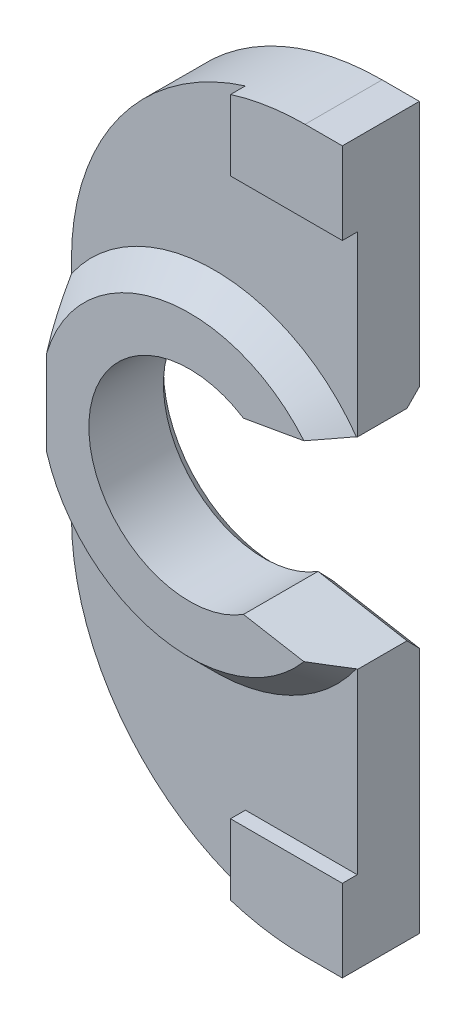
SolidWorks part; units mm, degrees
material "ABS"
ref_plane "Front Plane" through (0, 0, 0) normal (0, 0, 1) x (1, 0, 0)
ref_plane "Top Plane" through (0, 0, 0) normal (0, 1, 0) x (1, 0, 0)
ref_plane "Right Plane" through (0, 0, 0) normal (1, 0, 0) x (0, 0, -1)
sketch "Sketch2" plane through (0, 0, 0) normal (0, 0, 1) x (1, 0, 0)
  line L1 (5.75, -14.5) -> (4.25, -14.5)
  line L2 (5.75, -14.5) -> (5.75, -4.05)
  line L3 (5.75, 14.5) -> (4.25, 14.5)
  line L4 (-5.75, -4.5) -> (-5.75, 4.5)
  line L5 (5.75, -14.5) -> (1.4929, -3.7648) construction
  line L6 (5.75, 14.5) -> (1.606, 4.05) construction
  line L8 (5.75, 4.05) -> (5.75, 14.5)
  line L9 (0, 0) -> (-5.75, -14.5) construction
  line L10 (-1.4929, 3.7648) -> (-5.75, 14.5) construction
  line L11 (5.75, 4.05) -> (2.171, 3.4189)
  line L12 (5.75, -4.05) -> (2.171, -3.4189)
  arc A1 (4.25, -14.5) -> (-5.75, -4.5) centre (4.25, -4.5) cw
  arc A2 (-5.75, 4.5) -> (4.25, 14.5) centre (4.25, 4.5) cw
  arc A3 (2.171, 3.4189) -> (2.171, -3.4189) centre (0, 0) ccw
  point P0 (0, 0)
  dimension "D4" = 10
  dimension "D1" = 11.5
  dimension "D2" = 29
extrude "Boss-Extrude1" add sketch "Sketch2" along normal blind 2.5
sketch "Sketch3" plane through (0, 0, 2.5) normal (0, 0, 1) x (1, 0, 0)
  line L4 (-5.75, 4.5) -> (-5.75, -4.5) construction
  line L5 (-5.75, 1.7139) -> (-5.75, -1.7139)
  line L6 (2.171, 3.4189) -> (5.75, 4.05) construction
  line L7 (5.75, -4.05) -> (2.171, -3.4189) construction
  line L8 (2.171, 3.4189) -> (4.6037, 3.8479)
  line L9 (4.6037, -3.8479) -> (2.171, -3.4189)
  arc A1 (0, 4.05) -> (0, -4.05) centre (0, 0) ccw
  arc A2 (4.6037, 3.8479) -> (-5.75, 1.7139) centre (0, 0) ccw
  arc A3 (-5.75, -1.7139) -> (4.6037, -3.8479) centre (0, 0) ccw
  arc A4 (2.171, 3.4189) -> (2.171, -3.4189) centre (0, 0) ccw construction
  arc A5 (2.171, 3.4189) -> (2.171, -3.4189) centre (0, 0) ccw
  line M8 (-5.75, 4.5) -> (-5.75, -4.5)
  line M17 (5.75, -4.05) -> (2.171, -3.4189)
  arc M18 (2.171, -3.4189) -> (2.171, 3.4189) centre (0, 0) cw
  line M19 (2.171, 3.4189) -> (5.75, 4.05)
  dimension "D1" = 12
extrude "Boss-Extrude2" add sketch "Sketch3" along normal blind 1 contours A3 A2 M8 M17 M18 M19
sketch "Sketch4" plane through (0, 0, 2.5) normal (0, 0, 1) x (1, 0, 0)
  line L0 (5.75, 11.2) -> (1.25, 11.2)
  line L1 (1.25, 11.2) -> (1.25, 14.0394)
  line L5 (5.75, 4.05) -> (5.75, 14.5)
  line L6 (5.75, 14.5) -> (4.25, 14.5)
  line L7 (-5.75, 4.5) -> (-5.75, 1.7139)
  line L9 (5.75, 4.05) -> (5.75, 14.5)
  line L10 (5.75, 14.5) -> (4.25, 14.5)
  line L11 (-5.75, 4.5) -> (-5.75, 1.7139)
  line L15 (4.6037, 3.8479) -> (5.75, 4.05)
  line L16 (4.6037, 3.8479) -> (5.75, 4.05)
  arc A2 (4.6037, 3.8479) -> (-5.75, 1.7139) centre (0, 0) ccw
  arc A3 (4.25, 14.5) -> (-5.75, 4.5) centre (4.25, 4.5) ccw
  arc A4 (4.6037, 3.8479) -> (-5.75, 1.7139) centre (0, 0) ccw
  arc A5 (4.25, 14.5) -> (-5.75, 4.5) centre (4.25, 4.5) ccw
  line M9 (5.75, 4.05) -> (5.75, 14.5)
  line M10 (5.75, 14.5) -> (4.25, 14.5)
  arc M11 (4.25, 14.5) -> (-5.75, 4.5) centre (4.25, 4.5) ccw
  dimension "D2" = 4.5
  dimension "D3" = 3.3
  dimension "D1" = 0
extrude "Boss-Extrude3" add sketch "Sketch4" along normal blind 0.6 contours L1 L0 M9 M10 M11
mirror "Mirror1" about plane through (0, 0, 0) normal (0, 1, 0) of "Boss-Extrude3"
chamfer "Chamfer2" distance 1 angle 45 2 edges
chamfer "Chamfer3" distance 0.5 angle 45 3 edges at (3.9605, 3.7345, 0) (3.9605, -3.7345, 0) (-4.05, 0, 0)
